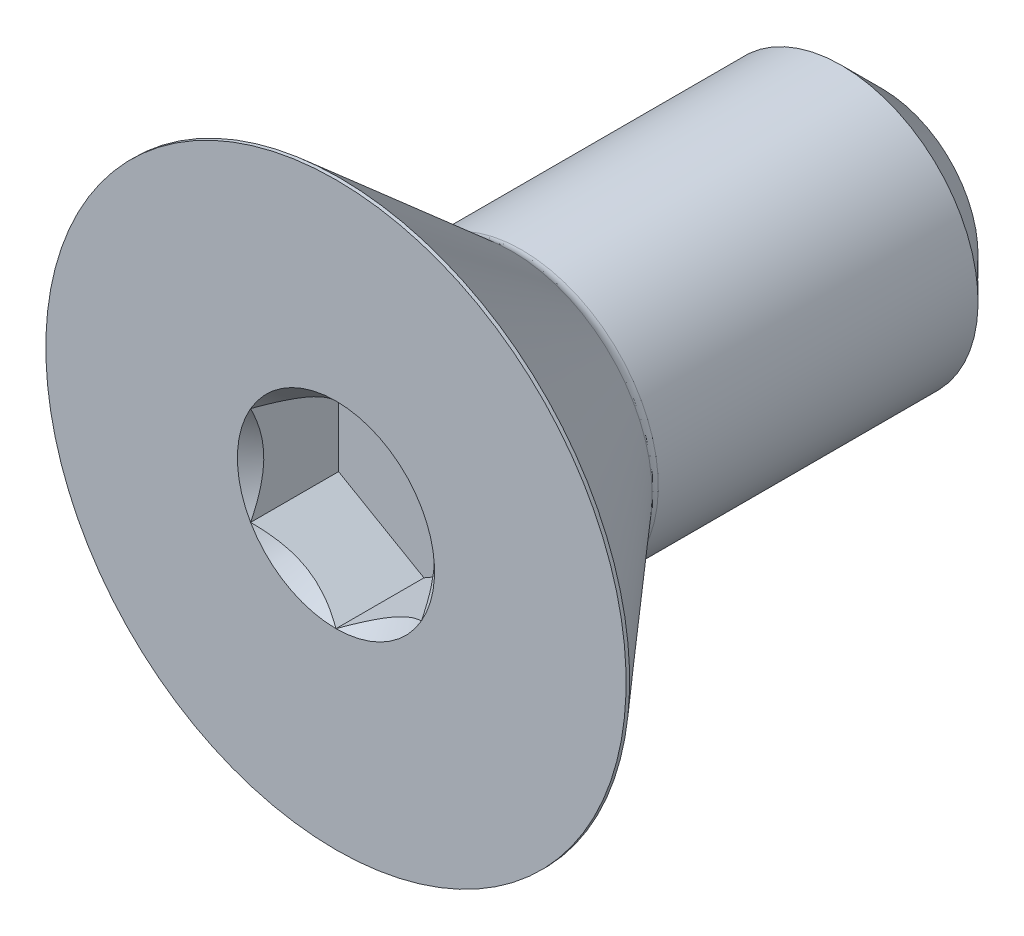
SolidWorks part; units mm, degrees
ref_plane "Front Plane" through (0, 0, 0) normal (0, 0, 1) x (1, 0, 0)
ref_plane "Top Plane" through (0, 0, 0) normal (0, 1, 0) x (1, 0, 0)
ref_plane "Right Plane" through (0, 0, 0) normal (1, 0, 0) x (0, 0, -1)
sketch "Sketch1" plane through (0, 0, 0) normal (1, 0, 0) x (0, 0, -1)
  line L0 (-6.35, 0) -> (6.35, 0) construction
  line L1 (-6.35, 0) -> (-6.35, 6.7437)
  line L2 (-6.35, 6.7437) -> (-6.2682, 6.7437)
  line L3 (-6.2682, 6.7437) -> (-2.2606, 3.2599)
  line L4 (-6.2682, -6.7437) -> (-2.2606, -3.2599)
  line L5 (6.35, 0) -> (6.35, 3.175)
  line L6 (6.35, 3.175) -> (-2.2606, 3.175)
  line L7 (5.3975, 3.175) -> (6.35, 2.2225)
  line L8 (6.2706, 3.3125) -> (6.9056, 2.2126) construction
  line L9 (6.9056, 2.2126) -> (7.5406, 3.3125) construction
  line L10 (7.5406, 3.3125) -> (6.2706, 3.3125) construction
  line L11 (6.3103, 3.2437) -> (7.5009, 3.2437)
  line L12 (7.5009, 3.2437) -> (6.985, 2.3501)
  line L13 (6.985, 2.3501) -> (6.8262, 2.3501)
  line L14 (6.8262, 2.3501) -> (6.3103, 3.2437)
  line L15 (6.9056, 2.3501) -> (6.9056, 2.2126) construction
  line L16 (6.35, 3.175) -> (7.4613, 3.175) construction
  line L17 (6.9056, 3.3125) -> (6.9056, 3.175) construction
  line L18 (6.35, -3.175) -> (-2.2606, -3.175)
  arc A0 (-2.2606, 3.2599) -> (-2.0334, 3.175) centre (-2.0334, 3.5213) ccw
  point P2 (0, 0)
  point P23 (-4.3053, 0)
  point P27 (6.9056, 3.2437)
  point P30 (4.445, -3.175)
  point P31 (-2.2606, 6.7437)
  point P34 (-6.2682, -6.7437)
  dimension "Length" = 12.7
  dimension "Head Height" = 4.0894
  dimension "Head Diameter" = 13.4874
  dimension "Countersink Angle" = 82
  dimension "Screw Size Decimal Equivalent" = 6.35
  dimension "Pitch" = 1.27
  dimension "D4" = 0.1588
  dimension "D3" = 45
  dimension "D5" = 0.9525
  dimension "D6" = 2.0447
  dimension "D1" = 1.905
  dimension "D7" = 0.0818
sketch "Sketch8" plane through (0, 0, 0) normal (0, 0, 1) x (1, 0, 0)
  line L1 (0, 2.2914) -> (-1.9844, 1.1457)
  line L2 (-1.9844, 1.1457) -> (-1.9844, -1.1457)
  line L3 (-1.9844, -1.1457) -> (0, -2.2914)
  line L4 (0, -2.2914) -> (1.9844, -1.1457)
  line L5 (1.9844, -1.1457) -> (1.9844, 1.1457)
  line L6 (1.9844, 1.1457) -> (0, 2.2914)
  circle A0 centre (0, 0) radius 1.9844 construction
  dimension "Drive Size" = 3.9688
sketch "Sketch2" plane through (0, 0, 0) normal (1, 0, 0) x (0, 0, -1)
  line L0 (-6.2682, 6.7437) -> (-2.2606, 3.2599) construction
  line L1 (-6.35, 0) -> (-6.35, 6.7437) construction
  line L2 (-6.2682, 6.7437) -> (-2.2606, 3.2599)
  line L3 (-6.35, 0) -> (-6.35, 6.7437)
  line L4 (-6.35, 6.7437) -> (-6.2682, 6.7437) construction
  line L5 (-6.35, 6.7437) -> (-6.2682, 6.7437)
  line L6 (-2.0334, 3.175) -> (5.3975, 3.175)
  line L7 (5.3975, 3.175) -> (6.35, 2.2225)
  line L8 (6.35, 2.2225) -> (6.35, 0)
  line L9 (6.35, 0) -> (-6.35, 0)
  arc A0 (-2.2606, 3.2599) -> (-2.0334, 3.175) centre (-2.0334, 3.5213) ccw construction
  arc A1 (-2.2606, 3.2599) -> (-2.0334, 3.175) centre (-2.0334, 3.5213) ccw
revolve "Revolve1" add sketch "Sketch2" angle 360 about L9
sketch "Sketch9" plane through (0, 0, 6.35) normal (0, 0, 1) x (1, 0, 0)
  line L0 (1.9844, -1.1457) -> (1.9844, 1.1457) construction
  line L1 (0, -2.2914) -> (1.9844, -1.1457) construction
  line L2 (-1.9844, -1.1457) -> (0, -2.2914) construction
  line L3 (-1.9844, 1.1457) -> (-1.9844, -1.1457) construction
  line L4 (0, 2.2914) -> (-1.9844, 1.1457) construction
  line L5 (1.9844, 1.1457) -> (0, 2.2914) construction
  line L6 (1.9844, -1.1457) -> (1.9844, 1.1457)
  line L7 (0, -2.2914) -> (1.9844, -1.1457)
  line L8 (-1.9844, -1.1457) -> (0, -2.2914)
  line L9 (-1.9844, 1.1457) -> (-1.9844, -1.1457)
  line L10 (0, 2.2914) -> (-1.9844, 1.1457)
  line L11 (1.9844, 1.1457) -> (0, 2.2914)
sketch "Sketch10" plane through (0, 0, 6.35) normal (0, 0, 1) x (1, 0, 0)
  circle A0 centre (0, 0) radius 2.2914
extrude "Cut-Extrude2" cut sketch "Sketch10" against normal up to vertex (2.0447 mm away) draft 45 up to point (0, 0, 4.3053)
extrude "Cut-Extrude1" cut sketch "Sketch9" against normal up to vertex (2.0447 mm away) up to point (0, 0, 4.3053)
ref_plane "Plane1" [suppressed] through (0, 0, 2.0334) normal (0, 0, 1) x (1, 0, 0)
split "Split1" [suppressed] bodies to split 111
sketch "Sketch3" [suppressed] plane through (0, 0, -6.35) normal (0, 0, -1) x (-1, 0, 0)
  circle A0 centre (0, 0) radius 3.175 construction
  circle A1 centre (0, 0) radius 3.175
curve "Helix/Spiral1" [suppressed] pitch 1.27 height 12.7 turns 10
sketch "Sketch4" [suppressed] plane through (0, 0, 0) normal (1, 0, 0) x (0, 0, -1)
  line L0 (6.3103, 3.2437) -> (7.5009, 3.2437) construction
  line L1 (6.8262, 2.3501) -> (6.3103, 3.2437) construction
  line L2 (6.985, 2.3501) -> (6.8262, 2.3501) construction
  line L3 (7.5009, 3.2437) -> (6.985, 2.3501) construction
  line L4 (6.3103, 3.2437) -> (7.5009, 3.2437)
  line L5 (6.8262, 2.3501) -> (6.3103, 3.2437)
  line L6 (6.985, 2.3501) -> (6.8262, 2.3501)
  line L7 (7.5009, 3.2437) -> (6.985, 2.3501)
sweep "Cut-Sweep1" [suppressed] cut profiles "Sketch4" path "Helix/Spiral1"
sketch "Sketch7" [suppressed] plane through (0, 0, 2.0334) normal (0, 0, 1) x (1, 0, 0)
  circle A0 centre (0, 0) radius 3.175
extrude "Boss-Extrude2" [suppressed] add sketch "Sketch7" against normal up to next draft 20
equation "\"D4@Sketch1\" = \"Pitch@Sketch1\" / 8"
equation "\"D5@Sketch1\"=\"Pitch@Sketch1\"*0.75"
equation "\"D4@Helix/Spiral1\"=\"Pitch@Sketch1\""
equation "\"D3@Helix/Spiral1\"=\"Length@Sketch1\""
equation "\"D6@Sketch1\"=\"Head Height@Sketch1\"/2"
equation "\"D1@Sketch1\"=\"Pitch@Sketch1\"*1.5"
equation "\"D7@Sketch1\"=\"Head Height@Sketch1\"*0.02"
